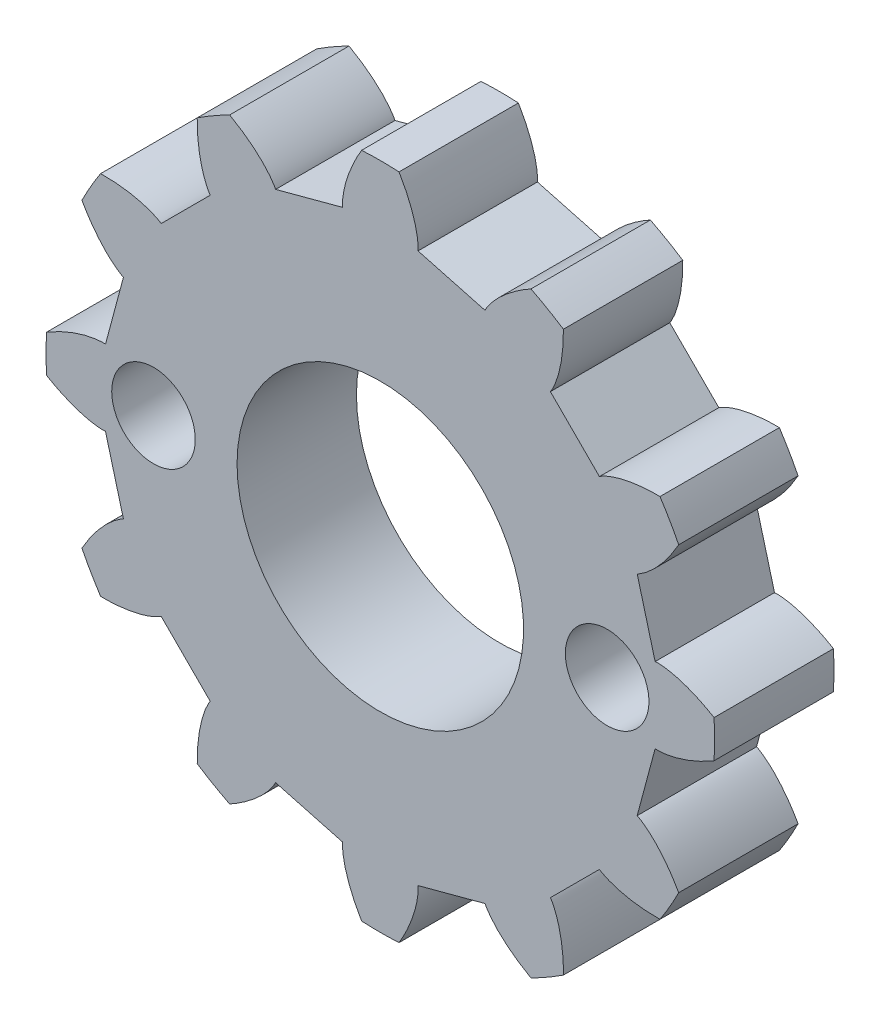
SolidWorks part; units mm, degrees
material "Plain Carbon Steel"
ref_plane "Front Plane" through (0, 0, 0) normal (0, 0, 1) x (1, 0, 0)
ref_plane "Top Plane" through (0, 0, 0) normal (0, 1, 0) x (1, 0, 0)
ref_plane "Right Plane" through (0, 0, 0) normal (1, 0, 0) x (0, 0, -1)
sketch "Sketch1" plane through (0, 0, 0) normal (0, 1, 0) x (1, 0, 0)
  line L0 (0, 0) -> (14, 0)
  line L1 (14, 0) -> (14, -5)
  line L2 (14, -5) -> (0, -5)
  line L3 (0, -5) -> (0, 0)
  line L4 (0, -1) -> (0, -4) construction
  dimension "D1" = 14
  dimension "D2" = 5
revolve "Revolve1" add sketch "Sketch1" angle 360 about L4
sketch "Sketch2" plane through (0, 0, 0) normal (0, 0, 1) x (1, 0, 0)
  spline S0 degree 4 poles (11.5098, 1.5803) (11.5136, 1.5807) (11.5245, 1.5819) (11.545, 1.5834) (11.5787, 1.5849) (11.6216, 1.5855) (11.6773, 1.5845) (11.7429, 1.5814) (11.8151, 1.5757) (11.8936, 1.5672) (11.972, 1.5566) (12.0501, 1.5442) (12.1278, 1.53) (12.2219, 1.5108) (12.3345, 1.4849) (12.4659, 1.4505) (12.6144, 1.4066) (12.7651, 1.3567) (12.9129, 1.3033) (13.0615, 1.2444) (13.2047, 1.1841) (13.3526, 1.1164) (13.4886, 1.0515) (13.64, 0.9733) (13.7618, 0.9086) (13.9211, 0.8176) (14.0148, 0.7621) (14.124, 0.6952) (14.1723, 0.6644) (14.202, 0.6455) knots 0 0 0 0 0 0.005377 0.015084 0.028532 0.04661 0.064855 0.092111 0.119476 0.146842 0.174209 0.201575 0.228941 0.256307 0.307035 0.361767 0.4165 0.471232 0.525964 0.580697 0.635429 0.690161 0.744894 0.799626 0.854358 0.909091 0.954545 1 1 1 1 1 construction
  spline S1 degree 4 poles (11.5098, 1.5803) (11.5136, 1.5807) (11.5245, 1.5819) (11.545, 1.5834) (11.5787, 1.5849) (11.6216, 1.5855) (11.6773, 1.5845) (11.7429, 1.5814) (11.8151, 1.5757) (11.8936, 1.5672) (11.972, 1.5566) (12.0501, 1.5442) (12.1278, 1.53) (12.2219, 1.5108) (12.3345, 1.4849) (12.4659, 1.4505) (12.6144, 1.4066) (12.7651, 1.3567) (12.9129, 1.3033) (13.0615, 1.2444) (13.2047, 1.1841) (13.3526, 1.1164) (13.4886, 1.0515) (13.64, 0.9733) (13.7618, 0.9086) (13.8866, 0.8373) (13.9472, 0.8019) (13.9781, 0.7836) knots 0 0 0 0 0 0.005377 0.015084 0.028532 0.04661 0.064855 0.092111 0.119476 0.146842 0.174209 0.201575 0.228941 0.256307 0.307035 0.361767 0.4165 0.471232 0.525964 0.580697 0.635429 0.690161 0.744894 0.799626 0.854358 0.909091 0.909091 0.909091 0.909091 0.909091
  spline S2 degree 4 poles (10.7579, 4.3863) (10.7615, 4.3879) (10.7714, 4.3923) (10.79, 4.4012) (10.8199, 4.4167) (10.8574, 4.4378) (10.9051, 4.4664) (10.9603, 4.5019) (11.02, 4.5429) (11.0838, 4.5896) (11.1463, 4.6379) (11.2078, 4.6878) (11.268, 4.7389) (11.3399, 4.8026) (11.4245, 4.8813) (11.521, 4.9768) (11.6276, 5.089) (11.7332, 5.2076) (11.8345, 5.3278) (11.9338, 5.453) (12.0276, 5.5769) (12.1219, 5.7094) (12.2072, 5.8337) (12.2992, 5.9771) (12.3723, 6.094) (12.4648, 6.2525) (12.5182, 6.3474) (12.5794, 6.46) (12.6058, 6.5107) (12.622, 6.5419) knots 0 0 0 0 0 0.005377 0.015084 0.028532 0.04661 0.064855 0.092111 0.119476 0.146842 0.174209 0.201575 0.228941 0.256307 0.307035 0.361767 0.4165 0.471232 0.525964 0.580697 0.635429 0.690161 0.744894 0.799626 0.854358 0.909091 0.954545 1 1 1 1 1 construction
  spline S3 degree 4 poles (10.7579, 4.3863) (10.7615, 4.3879) (10.7714, 4.3923) (10.79, 4.4012) (10.8199, 4.4167) (10.8574, 4.4378) (10.9051, 4.4664) (10.9603, 4.5019) (11.02, 4.5429) (11.0838, 4.5896) (11.1463, 4.6379) (11.2078, 4.6878) (11.268, 4.7389) (11.3399, 4.8026) (11.4245, 4.8813) (11.521, 4.9768) (11.6276, 5.089) (11.7332, 5.2076) (11.8345, 5.3278) (11.9338, 5.453) (12.0276, 5.5769) (12.1219, 5.7094) (12.2072, 5.8337) (12.2992, 5.9771) (12.3723, 6.094) (12.4448, 6.2181) (12.4796, 6.2791) (12.4971, 6.3104) knots 0 0 0 0 0 0.005377 0.015084 0.028532 0.04661 0.064855 0.092111 0.119476 0.146842 0.174209 0.201575 0.228941 0.256307 0.307035 0.361767 0.4165 0.471232 0.525964 0.580697 0.635429 0.690161 0.744894 0.799626 0.854358 0.909091 0.909091 0.909091 0.909091 0.909091
  spline S4 degree 4 poles (10.6821, 4.6693) (10.6871, 4.6507) (10.6969, 4.6141) (10.7102, 4.5642) (10.7499, 4.4163) (10.7648, 4.3605) (10.8113, 4.1871) (10.8381, 4.0872) (10.8742, 3.9524) (10.9064, 3.8321) (10.9432, 3.6947) (10.9769, 3.5692) (11.0101, 3.4453) (11.0416, 3.3274) (11.0741, 3.2063) (11.1068, 3.0843) (11.1415, 2.9547) (11.1783, 2.8176) (11.2144, 2.6827) (11.2529, 2.5391) (11.2929, 2.3896) (11.3356, 2.2303) (11.3723, 2.0933) (11.4172, 1.926) (11.4468, 1.8152) (11.4991, 1.6201) (11.5162, 1.5562) (11.5556, 1.4094) (11.57, 1.3555) (11.5802, 1.3176) (11.5853, 1.2983) knots 0 0 0 0 0 0.018951 0.037902 0.083333 0.123207 0.154566 0.191363 0.229806 0.266722 0.307549 0.348424 0.382797 0.411716 0.448648 0.491796 0.527759 0.566153 0.61051 0.653889 0.695217 0.748922 0.790536 0.831411 0.871976 0.916667 0.958835 0.979418 1 1 1 1 1 construction
  spline S5 degree 4 poles (10.7579, 4.3863) (10.7654, 4.3584) (10.7786, 4.3091) (10.8113, 4.1871) (10.8381, 4.0872) (10.8742, 3.9524) (10.9064, 3.8321) (10.9432, 3.6947) (10.9769, 3.5692) (11.0101, 3.4453) (11.0416, 3.3274) (11.0741, 3.2063) (11.1068, 3.0843) (11.1415, 2.9547) (11.1783, 2.8176) (11.2144, 2.6827) (11.2529, 2.5391) (11.2929, 2.3896) (11.3356, 2.2303) (11.3723, 2.0933) (11.4172, 1.926) (11.4468, 1.8152) (11.486, 1.669) (11.5014, 1.6116) (11.5098, 1.5803) knots 0.083333 0.083333 0.083333 0.083333 0.083333 0.123207 0.154566 0.191363 0.229806 0.266722 0.307549 0.348424 0.382797 0.411716 0.448648 0.491796 0.527759 0.566153 0.61051 0.653889 0.695217 0.748922 0.790536 0.831411 0.871976 0.916667 0.916667 0.916667 0.916667 0.916667
  spline S6 degree 4 poles (9.3779, 0.5257) (9.5199, 0.5337) (9.8554, 0.5525) (10.3394, 0.5796) (11.5261, 0.6461) (13.6059, 0.7627) (14.8795, 0.8341) (18.6766, 1.047) (20.9057, 1.1719) (24.2315, 1.3584) (26.7807, 1.5013) (29.5423, 1.6561) (31.8511, 1.7855) (34.272, 1.9212) (36.5893, 2.0512) (38.979, 2.1851) (41.3457, 2.3178) (43.5849, 2.4433) (45.7717, 2.5659) (47.8191, 2.6807) (49.7387, 2.7883) (51.542, 2.8894) (53.3069, 2.9883) (54.7633, 3.07) (56.428, 3.1633) (57.6091, 3.2295) (59.5097, 3.336) (60.3256, 3.3818) (62.3114, 3.4931) (62.9702, 3.53) (63.9674, 3.5859) (64.2116, 3.5996) (64.4045, 3.6104) (64.507, 3.6162) knots 0 0 0 0 0 0.010417 0.020833 0.041667 0.083333 0.13339 0.1844 0.242016 0.296484 0.342669 0.388178 0.431557 0.470492 0.514595 0.558618 0.603642 0.642943 0.676974 0.717014 0.753119 0.780568 0.810544 0.840688 0.866682 0.888463 0.916667 0.94344 0.975067 0.987533 0.993767 1 1 1 1 1 construction
  spline S7 degree 4 poles (13.9781, 0.7836) (14.5528, 0.8158) (15.6691, 0.8784) (18.6766, 1.047) (20.9057, 1.1719) (24.2315, 1.3584) (26.7807, 1.5013) (29.5423, 1.6561) (31.8511, 1.7855) (34.272, 1.9212) (36.5893, 2.0512) (38.979, 2.1851) (41.3457, 2.3178) (43.5849, 2.4433) (45.7717, 2.5659) (47.8191, 2.6807) (49.7387, 2.7883) (51.542, 2.8894) (53.3069, 2.9883) (54.7633, 3.07) (56.428, 3.1633) (57.6091, 3.2295) (59.0145, 3.3083) (59.582, 3.3401) (59.9058, 3.3582) knots 0.083333 0.083333 0.083333 0.083333 0.083333 0.13339 0.1844 0.242016 0.296484 0.342669 0.388178 0.431557 0.470492 0.514595 0.558618 0.603642 0.642943 0.676974 0.717014 0.753119 0.780568 0.810544 0.840688 0.866682 0.888463 0.916667 0.916667 0.916667 0.916667 0.916667
  spline S8 degree 4 poles (59.9936, 0.8849) (59.992, 0.9702) (59.9889, 1.1351) (59.9852, 1.4009) (59.9677, 1.9531) (59.9567, 2.3469) (59.9165, 3.1756) (59.8972, 3.5224) (59.8472, 4.309) (59.8091, 4.7834) (59.7552, 5.4355) (59.7016, 5.9812) (59.6386, 6.5898) (59.572, 7.1598) (59.4985, 7.7514) (59.4199, 8.3297) (59.3142, 9.0593) (59.1761, 9.9292) (58.9984, 10.9435) (58.7725, 12.0973) (58.5242, 13.2469) (58.2532, 14.3916) (57.9603, 15.53) (57.6442, 16.6639) (57.3075, 17.7888) (56.9464, 18.9113) (56.5672, 20.0192) (56.16, 21.1316) (55.7416, 22.2156) (55.2846, 23.3249) (54.8357, 24.3672) (54.377, 25.3651) (54.0472, 26.0631) (53.638, 26.8895) (53.474, 27.2141) (53.1008, 27.9394) (52.9077, 28.2973) (52.6507, 28.7764) (52.5189, 29.0126) (52.4396, 29.156) (52.3987, 29.2299) knots 0 0 0 0 0 0.010479 0.020959 0.041918 0.062626 0.083333 0.103175 0.123016 0.142857 0.162698 0.18254 0.202381 0.222222 0.242063 0.261905 0.281746 0.321429 0.361111 0.400794 0.440476 0.480159 0.519841 0.559524 0.599206 0.638889 0.678571 0.718254 0.757937 0.797619 0.837302 0.876984 0.896825 0.916667 0.937374 0.958082 0.979041 0.989521 1 1 1 1 1 construction
  spline S9 degree 4 poles (59.9058, 3.3582) (59.899, 3.4806) (59.8843, 3.7255) (59.8472, 4.309) (59.8091, 4.7834) (59.7552, 5.4355) (59.7016, 5.9812) (59.6386, 6.5898) (59.572, 7.1598) (59.4985, 7.7514) (59.4199, 8.3297) (59.3142, 9.0593) (59.1761, 9.9292) (58.9984, 10.9435) (58.7725, 12.0973) (58.5242, 13.2469) (58.2532, 14.3916) (57.9603, 15.53) (57.6442, 16.6639) (57.3075, 17.7888) (56.9464, 18.9113) (56.5672, 20.0192) (56.16, 21.1316) (55.7416, 22.2156) (55.2846, 23.3249) (54.8357, 24.3672) (54.377, 25.3651) (54.0472, 26.0631) (53.7227, 26.7185) (53.6143, 26.9352) (53.5591, 27.0446) knots 0.083333 0.083333 0.083333 0.083333 0.083333 0.103175 0.123016 0.142857 0.162698 0.18254 0.202381 0.222222 0.242063 0.261905 0.281746 0.321429 0.361111 0.400794 0.440476 0.480159 0.519841 0.559524 0.599206 0.638889 0.678571 0.718254 0.757937 0.797619 0.837302 0.876984 0.896825 0.916667 0.916667 0.916667 0.916667 0.916667
  spline S10 degree 4 poles (57.6821, 29.1265) (57.572, 29.0709) (57.3667, 28.9672) (57.1037, 28.8345) (56.2619, 28.4094) (55.6441, 28.0974) (54.0156, 27.2751) (53.2967, 26.9121) (51.5371, 26.0236) (50.2534, 25.3754) (48.3599, 24.4193) (46.515, 23.4877) (44.4582, 22.4491) (42.4499, 21.435) (40.4356, 20.4179) (38.4983, 19.4397) (36.6168, 18.4896) (34.7726, 17.5584) (32.9647, 16.6455) (31.0439, 15.6755) (29.1991, 14.744) (27.1967, 13.7329) (25.1823, 12.7157) (22.9096, 11.5682) (20.8628, 10.5346) (18.1968, 9.1884) (16.4053, 8.2838) (13.2579, 6.6945) (12.151, 6.1356) (10.2857, 5.1937) (9.26, 4.6758) (8.7999, 4.4435) (8.5191, 4.3017) (8.3831, 4.233) knots 0 0 0 0 0 0.007279 0.014558 0.029116 0.054016 0.083333 0.105636 0.130743 0.167468 0.204861 0.247819 0.28766 0.330173 0.370459 0.409856 0.445691 0.482639 0.520032 0.557203 0.600383 0.634615 0.678953 0.726696 0.774439 0.817842 0.868423 0.916667 0.958333 0.979167 0.989583 1 1 1 1 1 construction
  spline S11 degree 4 poles (53.5591, 27.0446) (53.3301, 26.929) (52.842, 26.6825) (51.5371, 26.0236) (50.2534, 25.3754) (48.3599, 24.4193) (46.515, 23.4877) (44.4582, 22.4491) (42.4499, 21.435) (40.4356, 20.4179) (38.4983, 19.4397) (36.6168, 18.4896) (34.7726, 17.5584) (32.9647, 16.6455) (31.0439, 15.6755) (29.1991, 14.744) (27.1967, 13.7329) (25.1823, 12.7157) (22.9096, 11.5682) (20.8628, 10.5346) (18.1968, 9.1884) (16.4053, 8.2838) (13.971, 7.0546) (12.9924, 6.5605) (12.4971, 6.3104) knots 0.083333 0.083333 0.083333 0.083333 0.083333 0.105636 0.130743 0.167468 0.204861 0.247819 0.28766 0.330173 0.370459 0.409856 0.445691 0.482639 0.520032 0.557203 0.600383 0.634615 0.678953 0.726696 0.774439 0.817842 0.868423 0.916667 0.916667 0.916667 0.916667 0.916667
extrude "Cut-Extrude2" cut sketch "Sketch2" against normal blind 6 and the other way blind 6
ref_axis "Axis1" through (0, 0, -0.25) along (0, 0, 1)
pattern_circular "CirPattern1" count 12 over 360 about axis through (0, 0, -0.25) along (0, 0, 1) of "Cut-Extrude2"
sketch "Sketch3" plane through (0, 0, 0) normal (0, 0, 1) x (1, 0, 0)
  circle A0 centre (0, 0) radius 6
  circle A1 centre (9.5, 0) radius 1.75
  circle A2 centre (-9.5, 0) radius 1.75
  dimension "D1" = 12
  dimension "D3" = 3.5
  dimension "D5" = 3.5
  dimension "D2" = 9.5
  dimension "D4" = 9.5
extrude "Cut-Extrude4" cut sketch "Sketch3" against normal blind 7 and the other way blind 7
equation "\"TrigProbe\"= cos(60)"
equation "\"SqrProbe\"= sqr(2)"
equation "\"AtnProbe\"= atn(1)"
equation "\"ToothCount\"= 12"
equation "\"DP\"= 12.7"
equation "\"PA\"= 14.5"
equation "\"PArad\"= \"PA\" * 3.14159265358979 / 180"
equation "\"Rb\"= \"ToothCount\" / \"DP\" * cos(\"PA\") / 2"
equation "\"Ra\"= (\"ToothCount\" + 2) / \"DP\" / 2"
equation "\"Tmax\"= sqr(\"Ra\" * \"Ra\" / (\"Rb\" * \"Rb\") - 1)"
equation "\"Delta\"= 3.14159265358979 / (2 * \"ToothCount\") + tan(\"PA\") - \"PArad\""
equation "\"Gamma\"= 2 * 3.14159265358979 / \"ToothCount\""
equation "\"ThetaL\"= atn(\"Tmax\") * 3.14159265358979 / 180 - \"Tmax\" + \"Delta\""
equation "\"ThetaU\"= \"Tmax\" - atn(\"Tmax\") * 3.14159265358979 / 180 - \"Delta\" + \"Gamma\""
equation "\"D1@Sketch1\" = \"Ra\""
equation "\"D1@CirPattern1\" = \"ToothCount\""
